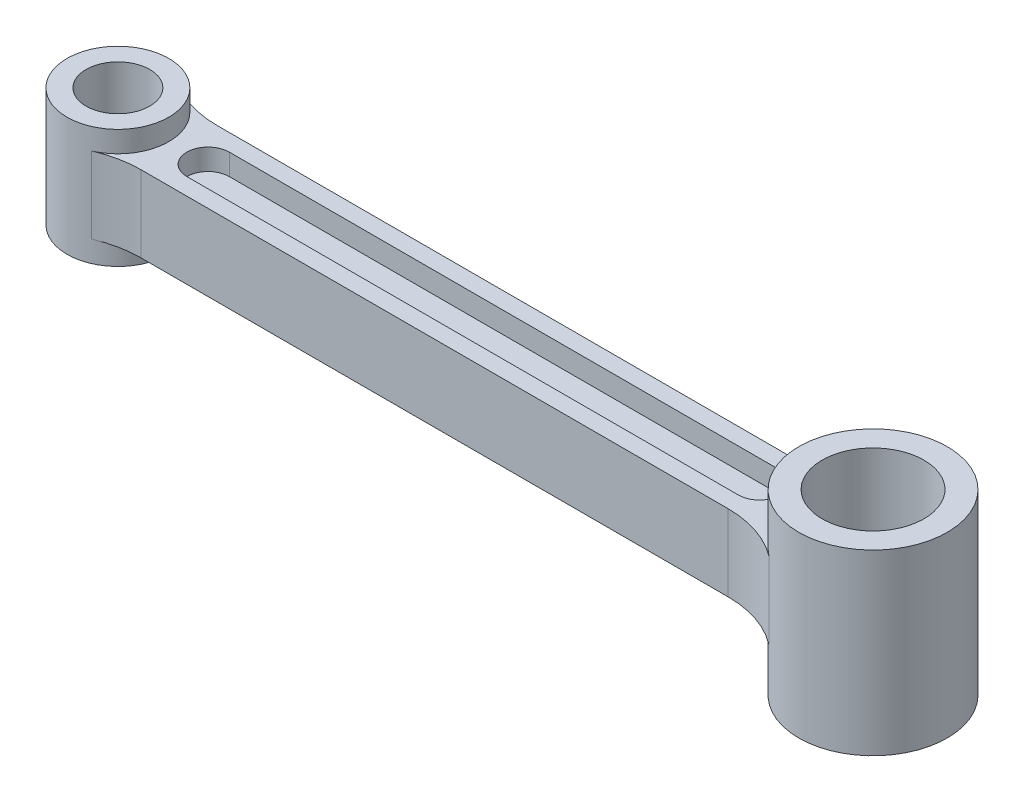
SolidWorks part; units mm, degrees
ref_plane "Front Plane" through (0, 0, 0) normal (0, 0, 1) x (1, 0, 0)
ref_plane "Top Plane" through (0, 0, 0) normal (0, 1, 0) x (1, 0, 0)
ref_plane "Right Plane" through (0, 0, 0) normal (1, 0, 0) x (0, 0, -1)
sketch "Sketch1" plane through (0, 0, 0) normal (0, 1, 0) x (1, 0, 0)
  line L0 (-39.9457, 9) -> (98.5024, 9)
  line L1 (-33.0832, 0) -> (96.9168, 0) construction
  line L2 (-39.9457, -9) -> (98.5024, -9)
  line L3 (-33.0832, 5) -> (96.9168, 5)
  line L4 (-33.0832, -5) -> (96.9168, -5)
  circle A0 centre (-54.3332, 0) radius 7.5
  circle A1 centre (-54.3332, 0) radius 12
  circle A2 centre (123.6668, 0) radius 12
  circle A3 centre (123.6668, 0) radius 17.5
  arc A4 (-39.9457, 9) -> (-49.5373, 11) centre (-39.9457, 33) cw
  arc A5 (98.5024, -9) -> (113.0553, -13.9157) centre (98.5024, -33) cw
  arc A6 (98.5024, 9) -> (113.0553, 13.9157) centre (98.5024, 33) ccw
  arc A7 (-39.9457, -9) -> (-49.5373, -11) centre (-39.9457, -33) ccw
  arc A8 (-33.0832, 5) -> (-33.0832, -5) centre (-33.0832, 0) ccw
  arc A9 (96.9168, -5) -> (96.9168, 5) centre (96.9168, 0) ccw
  point P20 (-40.2315, -8.8042)
  point P22 (31.9168, 0)
  point P27 (-42.3332, 0)
  point P28 (106.1668, 0)
  dimension "D1" = 24
  dimension "D2" = 15
  dimension "D3" = 35
  dimension "D4" = 24
  dimension "D6" = 24
  dimension "D7" = 24
  dimension "D5" = 178
  dimension "D8" = 9
  dimension "D9" = 10
  dimension "D10" = 130
  dimension "D11" = 9.25
extrude "Boss-Extrude1" add sketch "Sketch1" along normal mid plane 28 contours A1 A0 region at (-44.5784, 0, -6.3886)
extrude "Boss-Extrude2" add sketch "Sketch1<3>" along normal mid plane 42 separate body contours A3 A2 region at (131.2109, 0, -15.24)
sketch "Sketch1<3>" plane through (0, 0, 0) normal (0, 1, 0) x (1, 0, 0) same geometry as "Sketch1"
extrude "Boss-Extrude3" add sketch "Sketch1<4>" along normal mid plane 18 contours A7 L2 A5 A3 A6 L0 A4 A1 A9 L4 A8 L3 | L4 A9 L3 A8 region at (29.2783, 0, -7.3504)
sketch "Sketch1<4>" plane through (0, 0, 0) normal (0, 1, 0) x (1, 0, 0) same geometry as "Sketch1"
extrude "Cut-Extrude1" cut sketch "Sketch1<5>" against normal blind 5 from offset 9 contours L3 A9 L4 A8
sketch "Sketch1<5>" plane through (0, 0, 0) normal (0, 1, 0) x (1, 0, 0) same geometry as "Sketch1"
mirror "Mirror1" about plane through (0, 0, 0) normal (0, 1, 0) of "Cut-Extrude1"
